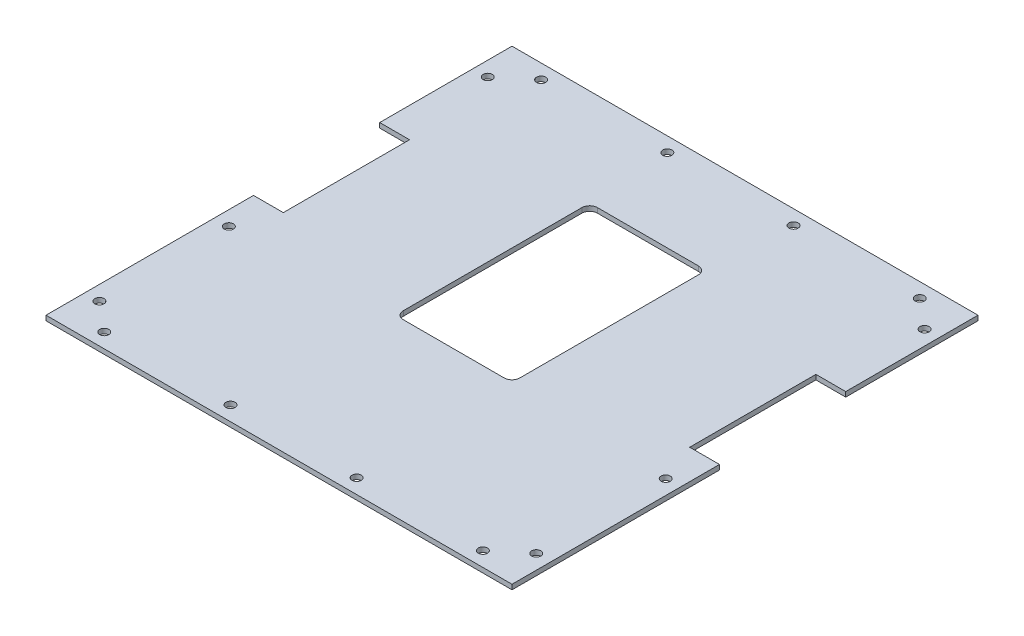
SolidWorks part; units mm, degrees
material "Thornel VCB-20 Carbon Cloth"
ref_plane "Front Plane" through (0, 0, 0) normal (0, 0, 1) x (1, 0, 0)
ref_plane "Top Plane" through (0, 0, 0) normal (0, 1, 0) x (1, 0, 0)
ref_plane "Right Plane" through (0, 0, 0) normal (1, 0, 0) x (0, 0, -1)
sketch "Sketch2" plane through (0, 0, 0) normal (0, 1, 0) x (1, 0, 0)
  line L0 (0, 0) -> (152.4, 0)
  line L1 (152.4, 0) -> (152.4, 152.4)
  line L2 (152.4, 152.4) -> (0, 152.4)
  line L3 (0, 152.4) -> (0, 0)
  dimension "D1" = 152.4
  dimension "D2" = 152.4
extrude "Boss-Extrude1" add sketch "Sketch2" along normal blind 1.5875
sketch "Sketch3" plane through (0, 1.5875, 0) normal (0, 1, 0) x (1, 0, 0)
  line L0 (0, 152.4) -> (4.7625, 152.4)
  line L1 (152.4, 152.4) -> (0, 152.4) construction
  line L2 (4.7625, 152.4) -> (4.7625, 0)
  line L3 (0, 0) -> (152.4, 0) construction
  line L4 (0, 152.4) -> (0, 147.6375)
  line L5 (0, 152.4) -> (0, 0) construction
  line L6 (0, 147.6375) -> (152.4, 147.6375)
  line L7 (152.4, 0) -> (152.4, 152.4) construction
  line L8 (152.4, 152.4) -> (147.6375, 152.4)
  line L9 (147.6375, 152.4) -> (147.6375, 0)
  line L10 (152.4, 0) -> (152.4, 4.7625)
  line L11 (152.4, 4.7625) -> (0, 4.7625)
  point P21 (4.7625, 139.7)
  point P23 (14.2875, 147.6375)
  point P24 (147.6375, 139.7)
  point P25 (138.1125, 4.7625)
  point P26 (4.7625, 12.7)
  dimension "D1" = 4.7625
  dimension "D2" = 4.7625
  dimension "D3" = 4.7625
  dimension "D4" = 4.7625
  dimension "D5" = 12.7
  dimension "D6" = 14.2875
  dimension "D7" = 12.7
  dimension "D8" = 14.2875
  dimension "D9" = 12.7
sketch "Sketch4" plane through (0, 1.5875, 0) normal (0, 1, 0) x (1, 0, 0)
  point P0 (14.2875, 147.6375)
  point P3 (147.6375, 139.7)
  point P6 (138.1125, 4.7625)
  point P9 (4.7625, 12.7)
sketch "Sketch6" plane through (0, 1.5875, 0) normal (0, 1, 0) x (1, 0, 0)
  line L0 (152.4, 4.7625) -> (0, 4.7625) construction
  line L1 (0, 152.4) -> (0, 0) construction
  point P0 (14.2875, 147.6375)
  point P3 (14.2875, 4.7625)
  dimension "D1" = 14.2875
hole_wizard "Ø3.0mm Dowel Hole1" positions "Sketch6" profile "Sketch7" hole size "Ø3.0" standard "ANSI Metric" end condition through all
sketch "Sketch7" plane through (14.2875, 1.5875, -147.6375) normal (1, 0, 0) x (0, 0, 1)
  line L0 (0, 0) -> (0, 1.5875)
  line L1 (0, 1.5875) -> (1.5, 1.5875)
  line L2 (1.5, 1.5875) -> (1.5, 0)
  line L5 (1.5, 0) -> (0, 0)
  line L11 (0, -6.35) -> (0, 107.95) construction
  dimension "Thru Hole Dia." = 3
  dimension "Thru Hole Depth" = 1.5875
sketch "Sketch8" plane through (0, 1.5875, 0) normal (0, 1, 0) x (1, 0, 0)
  point P0 (4.7625, 139.7)
  point P3 (147.6375, 139.7)
hole_wizard "Ø3.0mm Dowel Hole2" positions "Sketch8" profile "Sketch9" hole size "Ø3.0" standard "ANSI Metric" end condition through all
sketch "Sketch9" plane through (4.7625, 1.5875, -139.7) normal (1, 0, 0) x (0, 0, 1)
  line L0 (0, 0) -> (0, 1.5875)
  line L1 (0, 1.5875) -> (1.5, 1.5875)
  line L2 (1.5, 1.5875) -> (1.5, 0)
  line L5 (1.5, 0) -> (0, 0)
  line L11 (0, -6.35) -> (0, 107.95) construction
  dimension "Thru Hole Dia." = 3
  dimension "Thru Hole Depth" = 1.5875
pattern_linear "LPattern1" count 4 spacing 42.3333 along (0, 0, 1) skipping (1, 0) of "Ø3.0mm Dowel Hole2"
pattern_linear "LPattern2" count 4 spacing 41.275 along (1, 0, 0) of "Ø3.0mm Dowel Hole1"
sketch "Sketch12" plane through (0, 1.5875, 0) normal (0, 1, 0) x (1, 0, 0)
  line L10 (0, 152.4) -> (0, 0) construction
  line L11 (57.15, 120.65) -> (95.25, 120.65)
  line L12 (57.15, 120.65) -> (57.15, 57.15)
  line L13 (57.15, 57.15) -> (95.25, 57.15)
  line L14 (95.25, 120.65) -> (95.25, 57.15)
  line L15 (152.4, 152.4) -> (0, 152.4) construction
  line L16 (152.4, 0) -> (152.4, 152.4) construction
  dimension "D1" = 57.15
  dimension "D2" = 31.75
  dimension "D3" = 57.15
  dimension "D4" = 63.5
extrude "Cut-Extrude1" cut sketch "Sketch12" against normal blind 2.54 contours L14 L12 region at (76.2, 1.5875, -88.9)
fillet "Fillet2" radius 2.54 4 edges at (95.25, 0.7937, -57.15) (57.15, 0.7937, -57.15) (57.15, 0.7937, -120.65) (95.25, 0.7937, -120.65)
sketch "Sketch13" plane through (0, 1.5875, 0) normal (0, 1, 0) x (1, 0, 0)
  line L0 (152.4, 0) -> (152.4, 152.4) construction
  line L1 (152.4, 109.14) -> (142.65, 109.14)
  line L2 (152.4, 109.14) -> (152.4, 67.86)
  line L3 (152.4, 67.86) -> (142.65, 67.86)
  line L4 (142.65, 109.14) -> (142.65, 67.86)
  line L5 (152.4, 152.4) -> (0, 152.4) construction
  line L6 (76.2, 152.4) -> (76.2, 0) construction
  line L7 (0, 0) -> (152.4, 0) construction
  line L8 (0, 67.86) -> (9.75, 67.86)
  line L9 (9.75, 109.14) -> (9.75, 67.86)
  line L10 (0, 109.14) -> (9.75, 109.14)
  line L11 (0, 109.14) -> (0, 67.86)
  point P8 (147.525, 67.86)
  dimension "D1" = 43.26
  dimension "D2" = 41.28
  dimension "D3" = 9.75
extrude "Cut-Extrude2" cut sketch "Sketch13" against normal through all
